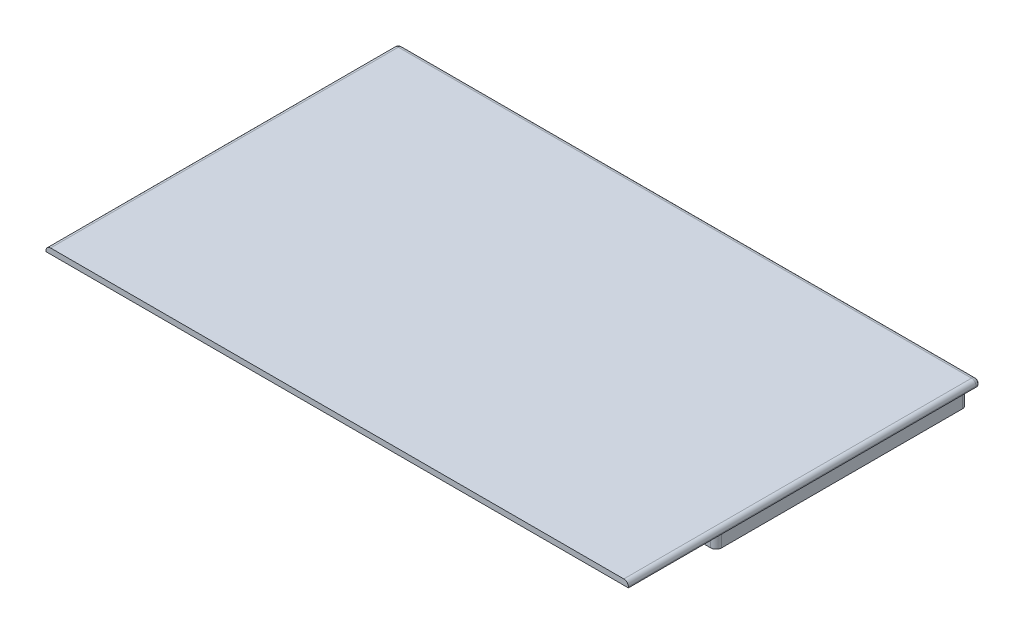
SolidWorks part; units mm, degrees
ref_plane "Front Plane" through (0, 0, 0) normal (0, 0, 1) x (1, 0, 0)
ref_plane "Top Plane" through (0, 0, 0) normal (0, 1, 0) x (1, 0, 0)
ref_plane "Right Plane" through (0, 0, 0) normal (1, 0, 0) x (0, 0, -1)
sketch "Sketch1" plane through (0, 0, 0) normal (0, 1, 0) x (1, 0, 0)
  line L0 (79.25, -36) -> (79.25, 36)
  line L1 (-78, -34.75) -> (78, -34.75)
  line L2 (-78, -34.75) -> (-78, 34.75)
  line L3 (-78, 34.75) -> (78, 34.75)
  line L4 (78, -34.75) -> (78, 34.75)
  line L5 (-78, -34.75) -> (78, 34.75) construction
  line L6 (-78, 34.75) -> (78, -34.75) construction
  line L7 (-79.25, 36) -> (79.25, 36)
  line L8 (-79.25, -36) -> (-79.25, 36)
  line L9 (-78, -36) -> (78, -36)
  line L10 (-78, -36) -> (-78, -86)
  line L11 (-78, -36) -> (78, -36)
  line L12 (-79.25, -36) -> (-79.25, -86)
  line L13 (-79.25, -86) -> (-79.25, -159)
  line L14 (79.25, -36) -> (79.25, -86)
  line L15 (78, -36) -> (78, -86)
  line L16 (-79.25, -36) -> (79.25, -36) construction
  line L17 (-78, -86) -> (-78, -100.5886)
  line L18 (79.25, -86) -> (79.25, -159)
  line L19 (78, -86) -> (78, -157.75)
  line L20 (79.25, -159) -> (-79.25, -159)
  line L21 (78, -159) -> (79.25, -159)
  line L22 (-78, -100.5886) -> (-78, -157.75)
  line L23 (-78, -157.75) -> (78, -157.75)
  line L24 (-78, -157.75) -> (78, -157.75) construction
  line L25 (0, -157.75) -> (0, -117.25)
  line L26 (-40, -117.25) -> (40, -117.25)
  line L27 (-34, -117.25) -> (34, -117.25)
  line L28 (-40, -117.25) -> (-34, -117.25) construction
  circle A0 centre (-37, -117.25) radius 3
  point P0 (0, 0)
  point P27 (0, -117.25)
  point P30 (0, -117.25)
  dimension "D1" = 156
  dimension "D2" = 69.5
  dimension "D4" = 50
  dimension "D5" = 195
  dimension "D6" = 1.25
  dimension "D7" = 40.5
  dimension "D8" = 80
  dimension "D9" = 68
  dimension "D3" = 1.25
sketch "Sketch2" plane through (0, 0, 0) normal (0, 1, 0) x (1, 0, 0)
  line L0 (-79.25, 36) -> (79.25, 36)
  line L1 (79.25, 36) -> (79.25, -159)
  line L2 (79.25, -159) -> (-79.25, -159)
  line L3 (-79.25, -159) -> (-79.25, 36)
extrude "Boss-Extrude1" add sketch "Sketch2" against normal blind 1.25
extrude "Boss-Extrude2" add sketch "Sketch1" along normal blind 105 contours L20 L18 L14 L0 L7 L8 L12 L13 L23 L22 L17 L10 L9 L15 L19 L4 L1 L2 L3 region at (78.9987, 0, 61)
sketch "Sketch4" plane through (0, 0, 0) normal (0, 1, 0) x (1, 0, 0)
  line L0 (-78, -157.75) -> (78, -157.75) construction
  line L1 (0, -157.75) -> (0, -117.75)
  line L2 (0, -5.0875) -> (0, 5.0875) construction
  line L3 (-34, -117.75) -> (34, -117.75)
  line L4 (-40.15, -117.75) -> (-39.575, -117.75)
  line L5 (-40.15, -117.75) -> (-39.575, -117.75) construction
  line L6 (34, -117.75) -> (34.575, -117.75) construction
  line L7 (-34.575, -117.75) -> (34.575, -117.75)
  line L8 (-34.575, -117.75) -> (-34, -117.75) construction
  line L9 (39.575, -117.75) -> (40.15, -117.75) construction
  line L10 (39.575, -117.75) -> (40.15, -117.75)
  circle A0 centre (-37.075, -117.75) radius 2.5
  circle A1 centre (37.075, -117.75) radius 2.5
  point P12 (0, -117.75)
  point P15 (0, -117.75)
  dimension "D1" = 40
  dimension "D2" = 68
  dimension "D3" = 80.3
extrude "Boss-Extrude3" add sketch "Sketch4" along normal blind 8 contours A0 | A1 region at (37.075, 0, 117.75) region at (-37.075, 0, 117.75)
fillet "Fillet2" radius 2 18 edges at (-78, 0, 0) (0, 0, -34.75) (78, 0, 0) (0, 0, 34.75) (0, 0, 36) (78, 0, 96.875) (0, 0, 157.75) (-78, 0, 96.875) (-37.075, 0, 115.25) (37.075, 0, 115.25) (78, 52.5, -34.75) (-78, 52.5, -34.75) (78, 52.5, 34.75) (-78, 52.5, 34.75) (-78, 52.5, 157.75) (78, 52.5, 157.75) (78, 52.5, 36) (-78, 52.5, 36)
sketch "Sketch5" plane through (0, 0, 36) normal (0, 0, 1) x (1, 0, 0)
  line L0 (-76, 105) -> (76, 105) construction
  line L2 (-76, 105) -> (-76, 2) construction
  line L3 (-58.75, 4.5) -> (58.75, 4.5)
  line L4 (-58.75, 4.5) -> (-58.75, 101.5)
  line L5 (-58.75, 101.5) -> (58.75, 101.5)
  line L6 (58.75, 4.5) -> (58.75, 101.5)
  line L7 (-58.75, 53) -> (58.75, 53)
  line L8 (-53.75, 101.5) -> (-53.75, 98)
  line L14 (-58.75, 98) -> (-53.75, 98)
  line L15 (0, 53) -> (0, 77.907)
  circle A0 centre (-53.75, 98) radius 1.55
  circle A1 centre (-53.75, 8) radius 1.55
  circle A2 centre (53.75, 8) radius 1.55
  circle A3 centre (53.75, 98) radius 1.55
  point P8 (0, 53.5)
  dimension "D1" = 97
  dimension "D2" = 117.5
  dimension "D3" = 17.25
  dimension "D4" = 3.5
  dimension "D5" = 5
  dimension "D6" = 3.5
extrude "Cut-Extrude1" cut sketch "Sketch5" against normal blind 8 contours L14 A0 L8 | L8 A0 L14 | A3 | A1 | A2 region at (-54.4078, 98.6578, 36) region at (-53.5307, 97.7807, 36) region at (-53.75, 8, 36) region at (53.75, 98, 36)
sketch "Sketch6" plane through (0, 0, 157.75) normal (0, 0, -1) x (-1, 0, 0)
  line L0 (-76, 2) -> (76, 2) construction
  line L1 (0, 2) -> (0, 22)
  line L2 (0, 5.0875) -> (0, -5.0875) construction
  circle A0 centre (0, 22) radius 8.25
  dimension "D1" = 20
extrude "Cut-Extrude2" cut sketch "Sketch6" against normal blind 8 contours A0 region at (-5.6686, 16.3314, 157.75)
sketch "Sketch8" plane through (-79.25, 0, 0) normal (-1, 0, 0) x (0, 0, 1)
  line L0 (159, 55) -> (116.5, 55)
  line L1 (159, -1.25) -> (159, 105) construction
  line L2 (116.5, 5) -> (116.5, 105)
  line L3 (159, 105) -> (-36, 105) construction
  line L4 (116.5, 55) -> (101.5, 55)
  line L5 (116.5, 55) -> (131.5, 55)
  line L7 (113, 58) -> (120, 58)
  line L8 (113, 58) -> (113, 72)
  line L9 (113, 72) -> (120, 72)
  line L10 (120, 58) -> (120, 72)
  line L11 (113, 58) -> (120, 72) construction
  line L12 (113, 72) -> (120, 58) construction
  circle A0 centre (101.5, 55) radius 3
  circle A1 centre (101.5, 65) radius 3
  circle A2 centre (101.5, 75) radius 3
  circle A3 centre (101.5, 85) radius 3
  circle A4 centre (131.5, 55) radius 3.75
  circle A5 centre (131.5, 75) radius 3.75
  point P9 (116.5, 55)
  point P13 (116.5, 65)
  dimension "D4" = 4
  dimension "D5" = 2
  dimension "D1" = 42.5
  dimension "D2" = 15
  dimension "D3" = 15
  dimension "D6" = 7
  dimension "D7" = 14
  dimension "D8" = 10
  dimension "D9" = 50
extrude "Cut-Extrude3" cut sketch "Sketch8" against normal blind 8 contours A0 | A2 | A3 | A1 | A5 | L8 L9 L10 L7 | A4 region at (-79.25, 55, 98.5849) region at (-79.25, 65, 101.5) region at (-79.25, 75, 101.5) region at (-79.25, 85, 101.5) region at (-79.25, 75, 131.5)
fillet "Fillet3" radius 1.25 4 edges at (0, -1.25, 159) (79.25, -1.25, 61.5) (0, -1.25, -36) (-79.25, -1.25, 61.5)
fillet "Fillet4" radius 1.25 8 edges at (-78.8839, -0.8839, 158.6339) (78.8839, -0.8839, 158.6339) (78.8839, -0.8839, -35.6339) (-78.8839, -0.8839, -35.6339) (-79.25, 52.5, 159) (79.25, 52.5, 159) (79.25, 52.5, -36) (-79.25, 52.5, -36)
sketch "Sketch11" plane through (79.25, 0, 0) normal (1, 0, 0) x (0, 0, -1)
  line L0 (-157.75, 105) -> (34.75, 0) construction
  line L1 (34.75, 105) -> (-157.75, 0)
  line L2 (87.175, 0) -> (-87.175, 0) construction
  line L4 (-111.5, 102.5) -> (-11.5, 102.5)
  line L5 (-111.5, 102.5) -> (-111.5, 2.5)
  line L6 (-111.5, 2.5) -> (-11.5, 2.5)
  line L7 (-11.5, 102.5) -> (-11.5, 2.5)
  line L8 (-111.5, 102.5) -> (-11.5, 2.5) construction
  line L9 (-111.5, 2.5) -> (-11.5, 102.5) construction
  line L10 (-99, 15) -> (-24, 15)
  line L11 (-99, 15) -> (-99, 90)
  line L12 (-99, 90) -> (-24, 90)
  line L13 (-24, 15) -> (-24, 90)
  line L14 (-99, 15) -> (-24, 90) construction
  line L15 (-99, 90) -> (-24, 15) construction
  circle A0 centre (-11.5, 102.5) radius 1.55
  circle A1 centre (-111.5, 102.5) radius 1.55
  circle A2 centre (-99, 90) radius 1.55
  circle A3 centre (-24, 90) radius 1.55
  circle A4 centre (-99, 15) radius 1.55
  circle A5 centre (-111.5, 2.5) radius 1.55
  circle A6 centre (-11.5, 2.5) radius 1.55
  circle A7 centre (-24, 15) radius 1.55
  point P9 (-61.5, 52.5)
  point P14 (-61.5, 52.5)
  dimension "D1" = 100
  dimension "D2" = 100
  dimension "D3" = 75
  dimension "D4" = 75
extrude "Cut-Extrude4" cut sketch "Sketch11" against normal blind 8 contours L7 A0 L4 | L4 A0 L7 | L13 A3 L12 | L12 A3 L13 | L6 A6 L7 | L5 A5 L6 | L6 A5 L5 | L11 A4 L10 | L10 A4 L11 | L10 A7 L13 | L13 A7 L10 | A1 | A2 | A6 region at (79.25, 101.8422, 12.1578) region at (79.25, 102.7193, 11.2807) region at (79.25, 2.2807, 11.2807) region at (79.25, 14.7807, 23.7807) region at (79.25, 15.6578, 24.6578) region at (79.25, 89.3422, 24.6578) region at (79.25, 90.2193, 23.7807) region at (79.25, 15.6578, 98.3422) region at (79.25, 14.7807, 99.2193) region at (79.25, 2.2807, 111.7193) region at (79.25, 3.1578, 110.8422)
sketch "Sketch12" plane through (0, 105, 0) normal (0, 1, 0) x (1, 0, 0)
  line L0 (0, -155.75) -> (0, -144.3132)
  line L1 (-78, -157.75) -> (-73, -157.75)
  line L2 (-78, -157.75) -> (-78, -152.75)
  line L3 (-78, -152.75) -> (-73, -152.75)
  line L4 (-73, -157.75) -> (-73, -152.75)
  line L5 (-76, -155.75) -> (76, -155.75) construction
  line L6 (0, -5.0875) -> (0, 5.0875) construction
  line L7 (78, -152.75) -> (73, -152.75)
  line L8 (73, -157.75) -> (73, -152.75)
  line L9 (78, -157.75) -> (73, -157.75)
  line L10 (78, -157.75) -> (78, -152.75)
  line M6 (76, -157.75) -> (-76, -157.75)
  arc M7 (-76, -157.75) -> (-78, -155.75) centre (-76, -155.75) cw
  line M8 (-78, -155.75) -> (-78, -38)
  line M12 (78, -38) -> (78, -155.75)
  arc M13 (78, -155.75) -> (76, -157.75) centre (76, -155.75) cw
  dimension "D1" = 5
  dimension "D2" = 5
extrude "Boss-Extrude5" add sketch "Sketch12" against normal up to surface (105 mm away) contours L8 L7 M6 M13 M12 | L4 L3 M6 M8 M7 region at (75.427, 105, 155.177) region at (-75.427, 105, 155.177) up to face at (0, 0, 96.875)
fillet "Fillet5" radius 1.25 14 edges at (78, 53.5, 152.75) (77.4142, 0.5858, 152.75) (74.5, 0, 152.75) (73, 0, 154.25) (73, 0.5858, 157.1642) (-73, 0, 154.25) (-73, 0.5858, 157.1642) (-74.5, 0, 152.75) (-77.4142, 0.5858, 152.75) (73, 53.5, 157.75) (73, 52.5, 152.75) (-73, 53.5, 157.75) (-78, 53.5, 152.75) (-73, 52.5, 152.75)
sketch "Sketch14" plane through (0, 105, 0) normal (0, 1, 0) x (1, 0, 0)
  line L0 (78, -38) -> (78, -151.5) construction
  line L1 (73.3661, -153.1161) -> (78, -153.1161)
  line L2 (73.3661, -153.1161) -> (73.3661, -157.75)
  line L3 (73.3661, -157.75) -> (78, -157.75)
  line L4 (78, -153.1161) -> (78, -157.75)
  line L5 (73.3661, -153.1161) -> (78, -157.75) construction
  line L6 (78, -157.75) -> (78.0536, -157.7607) construction
  line L7 (0, -157.75) -> (0, -147.0716)
  line L8 (-71.75, -157.75) -> (71.75, -157.75) construction
  line L9 (0, -58.4375) -> (0, 58.4375) construction
  arc A0 (74.25, -152.75) -> (73, -154) centre (74.25, -154) ccw construction
  circle A1 centre (75.6831, -155.4331) radius 1.525
  circle A2 centre (-75.6831, -155.4331) radius 1.525
extrude "Cut-Extrude5" cut sketch "Sketch14" against normal blind 8 contours A1 | A2 region at (75.6831, 105, 155.4331) region at (-75.6831, 105, 155.4331)
sketch "Sketch15" plane through (0, 105, 0) normal (0, 1, 0) x (1, 0, 0)
  line L16 (76, 33) -> (-76, 33)
  line L17 (-76.25, 32.75) -> (-76.25, -32.75)
  line L18 (-76, -33) -> (76, -33)
  line L19 (76.25, -32.75) -> (76.25, 32.75)
  line L20 (-77.5, 32.75) -> (-77.5, -32.75)
  line L21 (-76, -34.25) -> (76, -34.25)
  line L22 (77.5, -32.75) -> (77.5, 32.75)
  line L23 (76, 34.25) -> (-76, 34.25)
  line L24 (-77.5, 32.75) -> (-77.5, -32.75)
  line L25 (-76, -34.25) -> (76, -34.25)
  line L26 (77.5, -32.75) -> (77.5, 32.75)
  line L27 (76, 34.25) -> (-76, 34.25)
  arc A8 (78, 32.75) -> (76, 34.75) centre (76, 32.75) ccw construction
  arc A17 (-76, 33) -> (-76.25, 32.75) centre (-76, 32.75) ccw
  arc A18 (-76.25, -32.75) -> (-76, -33) centre (-76, -32.75) ccw
  arc A19 (76, -33) -> (76.25, -32.75) centre (76, -32.75) ccw
  arc A20 (76.25, 32.75) -> (76, 33) centre (76, 32.75) ccw
  arc A21 (-76, 34.25) -> (-77.5, 32.75) centre (-76, 32.75) ccw
  arc A22 (-77.5, -32.75) -> (-76, -34.25) centre (-76, -32.75) ccw
  arc A23 (76, -34.25) -> (77.5, -32.75) centre (76, -32.75) ccw
  arc A24 (77.5, 32.75) -> (76, 34.25) centre (76, 32.75) ccw
  arc A25 (-76, 34.25) -> (-77.5, 32.75) centre (-76, 32.75) ccw
  arc A26 (-77.5, -32.75) -> (-76, -34.25) centre (-76, -32.75) ccw
  arc A27 (76, -34.25) -> (77.5, -32.75) centre (76, -32.75) ccw
  arc A28 (77.5, 32.75) -> (76, 34.25) centre (76, 32.75) ccw
  dimension "D1" = 0.5
  dimension "D2" = 1.25
extrude "Boss-Extrude6" add sketch "Sketch15" against normal blind 5 separate body
sketch "Sketch19" plane through (0, 105, 0) normal (0, 1, 0) x (1, 0, 0)
  circle A2 centre (75.6831, -155.4331) radius 1.525
  circle A3 centre (75.6831, -155.4331) radius 1.525
  circle A5 centre (-75.6831, -155.4331) radius 1.525
  circle A6 centre (-75.6831, -155.4331) radius 1.525
  dimension "D1" = 0
  dimension "D2" = 0
extrude "Cut-Extrude10" cut sketch "Sketch19" along normal blind 176.5 and the other way blind 9
sketch "Sketch16" plane through (0, 105, 0) normal (0, 1, 0) x (1, 0, 0)
  line L8 (-79.25, 34.75) -> (-79.25, -157.75)
  line L9 (-78, -159) -> (78, -159)
  line L10 (79.25, -157.75) -> (79.25, 34.75)
  line L11 (78, 36) -> (-78, 36)
  line L12 (-79.25, 34.75) -> (-79.25, -157.75)
  line L13 (-78, -159) -> (78, -159)
  line L14 (79.25, -157.75) -> (79.25, 34.75)
  line L15 (78, 36) -> (-78, 36)
  arc A8 (-79.25, -157.75) -> (-78, -159) centre (-78, -157.75) ccw
  arc A9 (78, -159) -> (79.25, -157.75) centre (78, -157.75) ccw
  arc A10 (79.25, 34.75) -> (78, 36) centre (78, 34.75) ccw
  arc A11 (-78, 36) -> (-79.25, 34.75) centre (-78, 34.75) ccw
  arc A12 (-79.25, -157.75) -> (-78, -159) centre (-78, -157.75) ccw
  arc A13 (78, -159) -> (79.25, -157.75) centre (78, -157.75) ccw
  arc A14 (79.25, 34.75) -> (78, 36) centre (78, 34.75) ccw
  arc A15 (-78, 36) -> (-79.25, 34.75) centre (-78, 34.75) ccw
  dimension "D1" = 0
extrude "Boss-Extrude7" add sketch "Sketch16" along normal blind 1.5
sketch "Sketch17" plane through (0, 105, 0) normal (0, -1, 0) x (1, 0, 0)
  line L5 (97.501, -101.5148) -> (-116.8928, -101.5148)
  line L6 (97.501, -101.5148) -> (97.501, 210.2358)
  line L7 (97.501, 210.2358) -> (-116.8928, 210.2358)
  line L8 (78, -32.75) -> (78, 32.75)
  line L9 (76, 34.75) -> (-76, 34.75)
  line L10 (-78, 32.75) -> (-78, -32.75)
  line L11 (-76, -34.75) -> (76, -34.75)
  line L12 (78, -32.75) -> (78, 32.75)
  line L13 (76, 34.75) -> (-76, 34.75)
  line L14 (-78, 32.75) -> (-78, -32.75)
  line L15 (-76, -34.75) -> (76, -34.75)
  line L16 (-116.8928, -101.5148) -> (-116.8928, 210.2358)
  line L17 (97.501, -101.5148) -> (-116.8928, 210.2358) construction
  line L18 (97.501, 210.2358) -> (-116.8928, -101.5148) construction
  arc A8 (78, 32.75) -> (76, 34.75) centre (76, 32.75) ccw
  arc A9 (-76, 34.75) -> (-78, 32.75) centre (-76, 32.75) ccw
  arc A10 (-78, -32.75) -> (-76, -34.75) centre (-76, -32.75) ccw
  arc A11 (76, -34.75) -> (78, -32.75) centre (76, -32.75) ccw
  arc A12 (78, 32.75) -> (76, 34.75) centre (76, 32.75) ccw
  arc A13 (-76, 34.75) -> (-78, 32.75) centre (-76, 32.75) ccw
  arc A14 (-78, -32.75) -> (-76, -34.75) centre (-76, -32.75) ccw
  arc A15 (76, -34.75) -> (78, -32.75) centre (76, -32.75) ccw
  point P2 (-9.6959, 54.3605)
  dimension "D1" = 0
extrude "Cut-Extrude6" cut sketch "Sketch17" along normal blind 142.5
sketch "Sketch18" plane through (0, 100, 0) normal (0, -1, 0) x (1, 0, 0)
  line L1 (-421.9306, -105.0953) -> (421.9306, -105.0953)
  line L2 (-421.9306, -105.0953) -> (-421.9306, 105.0953)
  line L3 (-421.9306, 105.0953) -> (421.9306, 105.0953)
  line L4 (421.9306, -105.0953) -> (421.9306, 105.0953)
  line L5 (-421.9306, -105.0953) -> (421.9306, 105.0953) construction
  line L6 (-421.9306, 105.0953) -> (421.9306, -105.0953) construction
  point P0 (0, 0)
extrude "Cut-Extrude7" cut sketch "Sketch18" along normal blind 211.5
fillet "Fillet6" radius 1.25 8 edges at (0, 106.5, -36) (78.8839, 106.5, -35.6339) (79.25, 106.5, 61.5) (78.8839, 106.5, 158.6339) (0, 106.5, 159) (-78.8839, 106.5, 158.6339) (-79.25, 106.5, 61.5) (-78.8839, 106.5, -35.6339)
sketch "Sketch21" plane through (0, 106.5, 0) normal (0, 1, 0) x (1, 0, 0)
  line L0 (-78.8839, -158.6339) -> (-75.6807, -155.4307)
  line L1 (0, -159) -> (0, -145.5027)
  line L2 (78, -159) -> (-78, -159) construction
  line L3 (0, -3.575) -> (0, 3.575) construction
  arc A0 (-79.25, -157.75) -> (-78, -159) centre (-78, -157.75) ccw construction
  circle A1 centre (-75.6807, -155.4307) radius 1.525
  circle A2 centre (75.6807, -155.4307) radius 1.525
  dimension "D1" = 4.53
extrude "Cut-Extrude11" cut sketch "Sketch21" against normal blind 46.5 contours A1 | A2
sketch "Sketch22" plane through (0, 106.5, 0) normal (0, 1, 0) x (1, 0, 0)
  line L0 (53, -122.75) -> (-53, -122.75)
  line L1 (-78, -157.75) -> (-53, -157.75)
  line L2 (-78, -157.75) -> (-78, -122.75)
  line L3 (-78, -122.75) -> (-53, -122.75)
  line L4 (-53, -157.75) -> (-53, -122.75)
  line L6 (53, -124.25) -> (53, -121.25)
  line L7 (53, -122.75) -> (48, -122.75)
  circle A0 centre (-53, -122.75) radius 1.525
  circle A1 centre (53, -121.25) radius 0.5
  circle A2 centre (53, -124.25) radius 0.5
  circle A3 centre (48, -122.75) radius 1
  point P9 (0, -122.75)
  point P11 (53, -122.75)
  dimension "D3" = 3
  dimension "D4" = 5
  dimension "D1" = 25
  dimension "D2" = 35
extrude "Cut-Extrude12" cut sketch "Sketch22" against normal blind 46.5 contours L3 A0 L4 | L4 A0 L3 | A2 | A1 | L7 A3 L0 | L0 A3 L7 | L4 A0 L0 region at (-52.3528, 106.5, 123.3972) region at (-53, 106.5, 122.1028) region at (48, 106.5, 123.1744) region at (48, 106.5, 122.3256) region at (53.3436, 106.5, 123.9064) region at (52.6564, 106.5, 120.9064) region at (-53.6472, 106.5, 123.3972)
sketch "Sketch23" plane through (0, 105, 0) normal (0, -1, 0) x (1, 0, 0)
  line L1 (-106.4259, 59.8786) -> (117.9234, 59.8786)
  line L2 (-106.4259, 59.8786) -> (-106.4259, 79.8786)
  line L3 (-106.4259, 79.8786) -> (117.9234, 79.8786)
  line L4 (117.9234, 59.8786) -> (117.9234, 79.8786)
  dimension "D1" = 20
extrude "Cut-Extrude13" cut sketch "Sketch23" against normal blind 108
sketch "Sketch24" plane through (0, 0, 79.8786) normal (0, 0, -1) x (-1, 0, 0)
  line L0 (-76, 105) -> (76, 105) construction
  line L1 (-118.449, 63.4) -> (105.3789, 63.4)
  line L2 (-118.449, 63.4) -> (-118.449, 146.6)
  line L3 (-118.449, 146.6) -> (105.3789, 146.6)
  line L4 (105.3789, 63.4) -> (105.3789, 146.6)
  line L5 (-118.449, 63.4) -> (105.3789, 146.6) construction
  line L6 (-118.449, 146.6) -> (105.3789, 63.4) construction
  point P0 (-6.535, 105)
extrude "Cut-Extrude14" cut sketch "Sketch24" against normal blind 108
